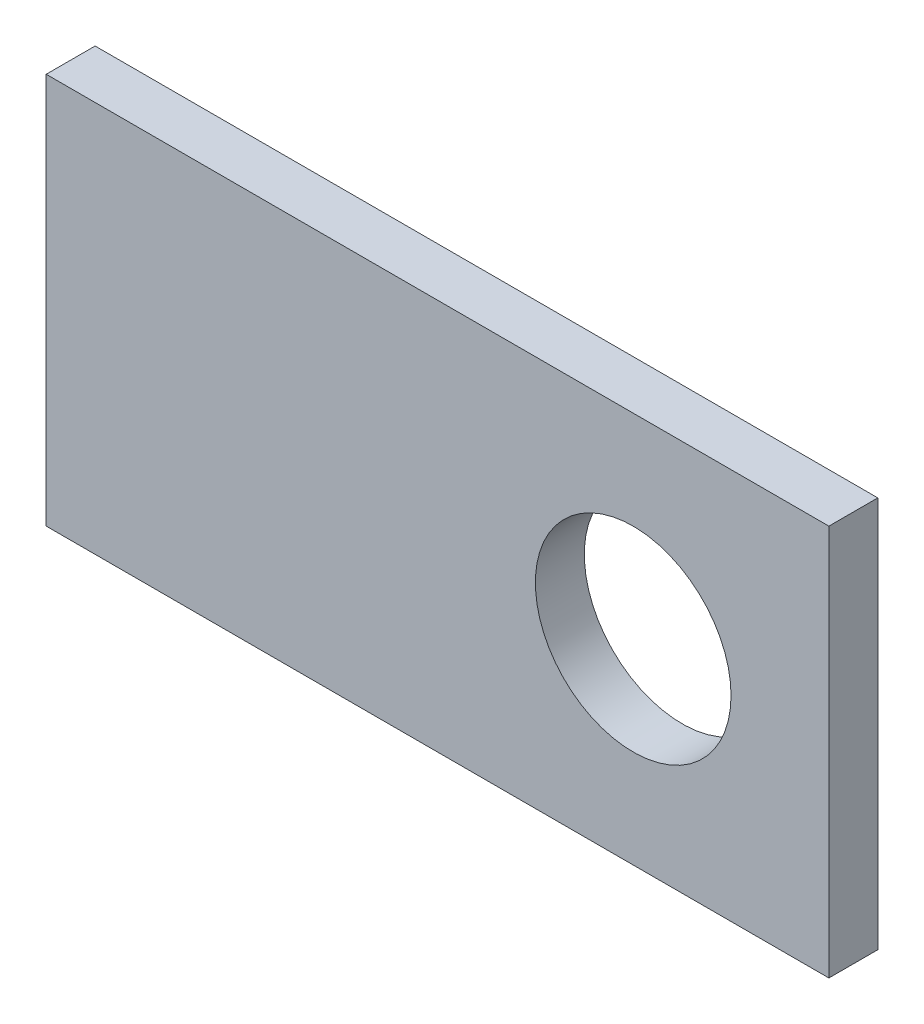
SolidWorks part; units mm, degrees
ref_plane "Front" through (0, 0, 0) normal (0, 0, 1) x (1, 0, 0)
ref_plane "Top" through (0, 0, 0) normal (0, 1, 0) x (1, 0, 0)
ref_plane "Right" through (0, 0, 0) normal (1, 0, 0) x (0, 0, -1)
sketch "Sketch1" plane through (0, 0, 0) normal (0, 0, 1) x (1, 0, 0)
  line L1 (0, 0) -> (50.8, 0)
  line L2 (0, 0) -> (0, 25.4)
  line L3 (0, 25.4) -> (50.8, 25.4)
  line L4 (50.8, 0) -> (50.8, 25.4)
  line L5 (0, 0) -> (50.8, 25.4) construction
  line L6 (0, 25.4) -> (50.8, 0) construction
  circle A0 centre (38.1, 12.7) radius 6.35
  point P4 (25.4, 12.7)
  dimension "D3" = 12.7
  dimension "D1" = 25.4
  dimension "D2" = 50.8
  dimension "D4" = 12.7
extrude "Boss-Extrude1" add sketch "Sketch1" along normal blind 3.175
